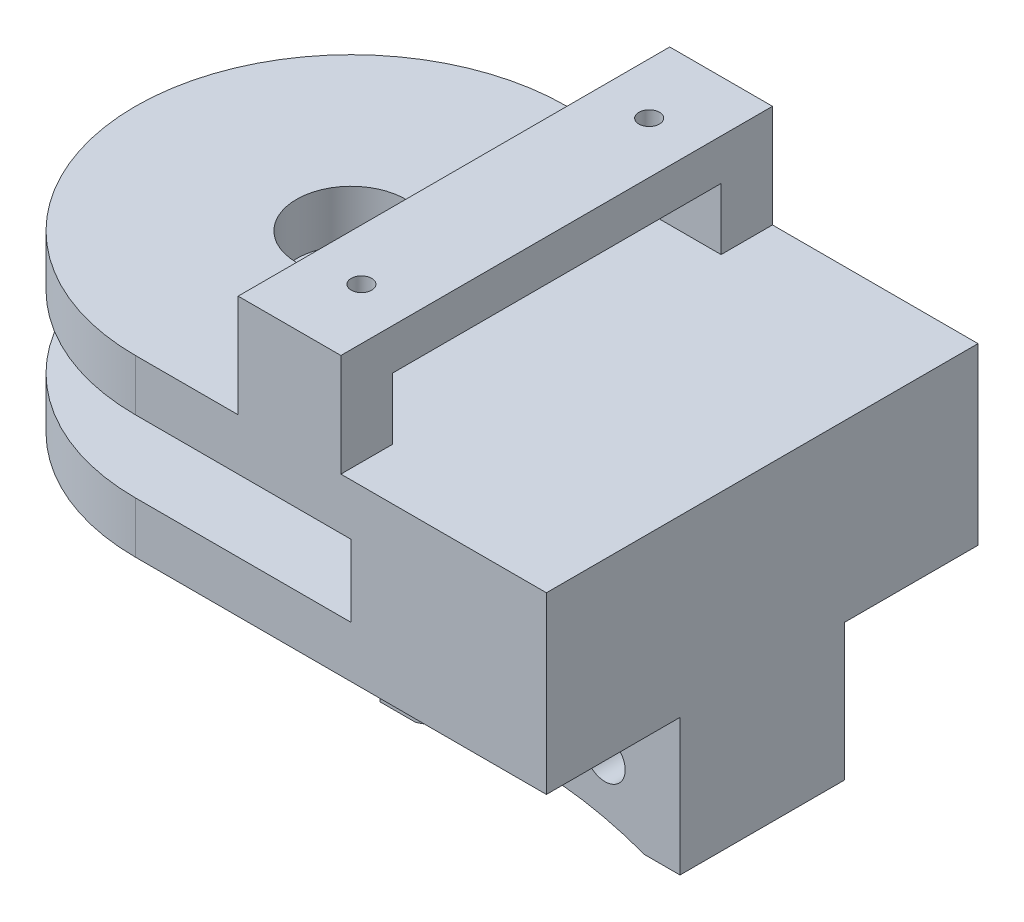
SolidWorks part; units mm, degrees
ref_plane "Front Plane" through (0, 0, 0) normal (0, 0, 1) x (1, 0, 0)
ref_plane "Top Plane" through (0, 0, 0) normal (0, 1, 0) x (1, 0, 0)
ref_plane "Right Plane" through (0, 0, 0) normal (1, 0, 0) x (0, 0, -1)
sketch "Sketch1" plane through (0, 0, 0) normal (0, 1, 0) x (1, 0, 0)
  line L0 (0, -13.335) -> (25.4, -13.335)
  line L1 (0, 13.335) -> (25.4, 13.335)
  line L2 (25.4, 13.335) -> (25.4, -13.335)
  circle A0 centre (0, 0) radius 12.7 construction
  circle A1 centre (0, 0) radius 13.335 construction
  circle A2 centre (0, 0) radius 3.3782
  arc A3 (11.5484, 6.6675) -> (11.5484, -6.6675) centre (0, 0) ccw construction
  arc A4 (0, 13.335) -> (0, -13.335) centre (0, 0) ccw
  dimension "D1" = 25.4
  dimension "D2" = 0.635
  dimension "D4" = 6.7564
  dimension "D3" = 25.4
extrude "Boss-Extrude1" add sketch "Sketch1" along normal blind 3.175 contours A3 A2 region at (7.6257, 0, 0)
sketch "Sketch2" plane through (0, 0, 0) normal (0, -1, 0) x (-1, 0, 0)
  line L3 (-25.4, 13.335) -> (-25.4, -13.335)
  line L5 (-13.335, 0) -> (-13.335, 13.335)
  line L6 (-25.4, 13.335) -> (-13.335, 13.335)
  line L7 (-13.335, 0) -> (-13.335, -13.335)
  line L8 (0, -13.335) -> (-25.4, -13.335) construction
  line L9 (-13.335, -13.335) -> (-25.4, -13.335)
  arc A3 (0, 13.335) -> (0, -13.335) centre (0, 0) ccw construction
extrude "Boss-Extrude2" add sketch "Sketch2" along normal blind 4.445 contours L3 L9 L7 L5 L6
ref_plane "Plane2" through (0, -2.2225, 0) normal (0, -1, 0) x (-1, 0, 0)
mirror "Mirror2" about plane through (0, -2.2225, 0) normal (0, -1, 0) of "Boss-Extrude1"
sketch "Sketch7" plane through (0, -7.62, 0) normal (0, -1, 0) x (-1, 0, 0)
  line L0 (-25.4, 13.335) -> (-25.4, 5.08) construction
  line L1 (-25.4, 13.335) -> (-25.4, -13.335) construction
  line L2 (0, 0) -> (-25.4, 0) construction
  line L3 (-25.4, -13.335) -> (-25.4, -5.08) construction
  line L5 (-25.4, 5.08) -> (-6.858, 5.08)
  line L6 (-25.4, 5.08) -> (-25.4, -5.08)
  line L7 (-25.4, -5.08) -> (-6.858, -5.08)
  line L8 (-6.858, 5.08) -> (-6.858, -5.08)
  dimension "D1" = 8.255
  dimension "D2" = 18.542
extrude "Boss-Extrude4" add sketch "Sketch7" along normal blind 8.4391
sketch "Sketch8" plane through (0, 0, -5.08) normal (0, 0, -1) x (-1, 0, 0)
  line L0 (-16.129, -7.62) -> (-16.129, -16.0591) construction
  line L1 (-16.129, -16.0591) -> (-25.4, -16.0591) construction
  line L2 (-20.7645, -16.0591) -> (-20.7645, -7.62) construction
  line L3 (-6.858, -7.62) -> (-25.4, -7.62) construction
  line L4 (-6.858, -16.0591) -> (-25.4, -16.0591) construction
  line L5 (0, -7.62) -> (-25.4, -7.62) construction
  circle A0 centre (-20.7645, -12.1285) radius 1.25
  circle A1 centre (-11.4935, -12.1285) radius 1.25
  dimension "D1" = 2.5
  dimension "D2" = 4.5085
extrude "Cut-Extrude3" cut sketch "Sketch8" against normal through all
sketch "Sketch9" plane through (0, 0, -5.08) normal (0, 0, -1) x (-1, 0, 0)
  line L0 (-16.129, -16.0591) -> (-16.129, -35.1091) construction
  line L1 (-6.858, -16.0591) -> (-25.4, -16.0591) construction
  line L2 (-16.129, -16.0591) -> (-16.129, -14.7891) construction
  circle A0 centre (-16.129, -35.1091) radius 20.32
  dimension "D1" = 1.27
  dimension "D2" = 19.05
extrude "Cut-Extrude4" cut sketch "Sketch9" against normal through all
sketch "Sketch11" plane through (0, 3.175, 0) normal (0, 1, 0) x (1, 0, 0)
  line L0 (0, 0) -> (25.4, 0) construction
  line L5 (6.35, -13.335) -> (6.35, 13.335) construction
  line L6 (0, -13.335) -> (25.4, -13.335) construction
  line L7 (25.4, 13.335) -> (25.4, -13.335) construction
  line L12 (0, 13.335) -> (25.4, 13.335) construction
  line L14 (6.35, 10.16) -> (12.7, 10.16)
  line L15 (6.35, -13.335) -> (12.7, -13.335) construction
  line L16 (6.35, -13.335) -> (6.35, 13.335) construction
  line L21 (6.35, 13.335) -> (12.7, 13.335) construction
  line L22 (12.7, -13.335) -> (12.7, 13.335) construction
  line L23 (6.35, -13.335) -> (12.7, -13.335)
  line L24 (6.35, -13.335) -> (6.35, -10.16)
  line L25 (6.35, -10.16) -> (12.7, -10.16)
  line L26 (12.7, -13.335) -> (12.7, -10.16)
  line L27 (12.7, 13.335) -> (12.7, 10.16)
  line L28 (6.35, 13.335) -> (12.7, 13.335)
  line L29 (6.35, 13.335) -> (6.35, 10.16)
  dimension "D1" = 6.35
  dimension "D2" = 6.35
  dimension "D3" = 3.175
extrude "Boss-Extrude8" add sketch "Sketch11" along normal blind 3.81 contours L24 L23 L26 L25 | L14 L27 L28 L29
sketch "Sketch14" plane through (0, 6.985, 0) normal (0, 1, 0) x (1, 0, 0)
  line L0 (9.525, 13.335) -> (9.525, -13.335) construction
  line L1 (12.7, -13.335) -> (6.35, -13.335)
  line L2 (12.7, -13.335) -> (12.7, 13.335)
  line L3 (12.7, 13.335) -> (6.35, 13.335)
  line L4 (6.35, -13.335) -> (6.35, 13.335)
  line L5 (0, 0) -> (25.4, 0) construction
  line L6 (25.4, 13.335) -> (25.4, -13.335) construction
  circle A0 centre (9.525, 8.89) radius 0.635
  circle A1 centre (9.525, -8.89) radius 0.635
  dimension "D1" = 1.27
  dimension "D2" = 4.445
extrude "Boss-Extrude9" add sketch "Sketch14" along normal blind 2.54
